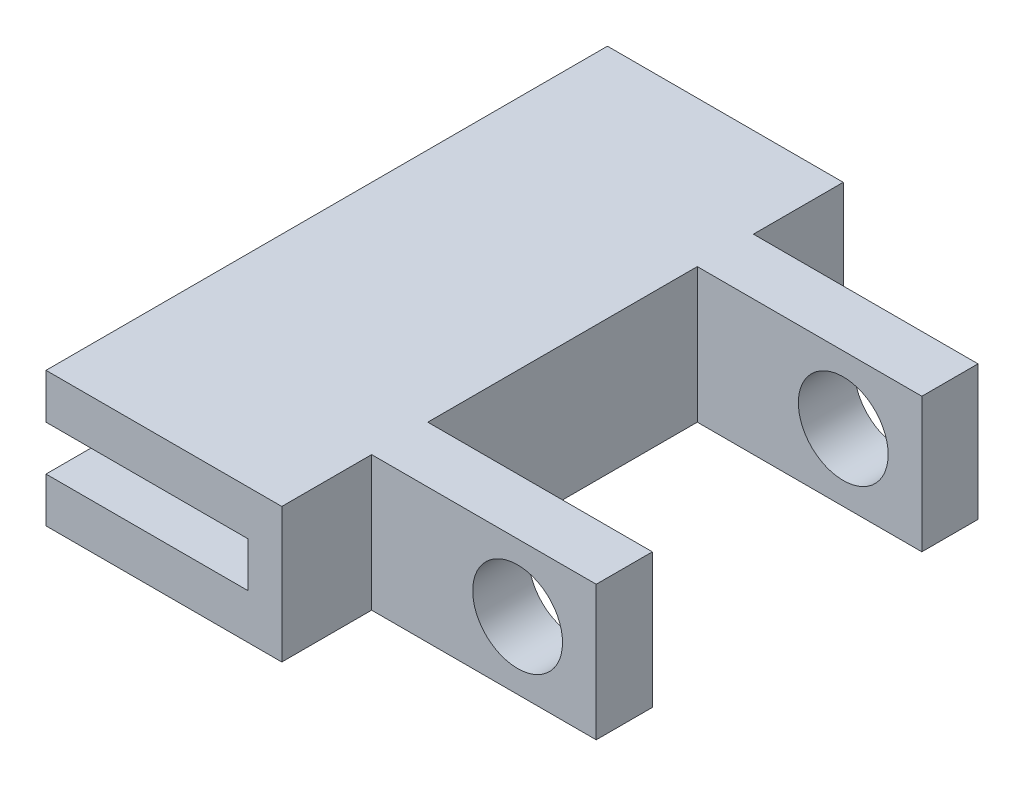
SolidWorks part; units mm, degrees
ref_plane "前视基准面" through (0, 0, 0) normal (0, 0, 1) x (1, 0, 0)
ref_plane "上视基准面" through (0, 0, 0) normal (0, 1, 0) x (1, 0, 0)
ref_plane "右视基准面" through (0, 0, 0) normal (1, 0, 0) x (0, 0, -1)
sketch "草图1" plane through (0, 0, 0) normal (0, 0, 1) x (1, 0, 0)
  line L0 (-12.5533, 0) -> (5.4467, 0)
  line L1 (5.4467, 0) -> (5.4467, 4)
  line L2 (5.4467, 4) -> (-12.5533, 4)
  line L3 (-12.5533, 8) -> (8.4467, 8)
  line L4 (8.4467, 8) -> (8.4467, -4)
  line L5 (8.4467, -4) -> (-12.5533, -4)
  line L6 (-12.5533, -4) -> (-12.5533, 0)
  line L7 (-12.5533, 4) -> (-12.5533, 8)
  dimension "D1" = 18
  dimension "D2" = 4
  dimension "D3" = 4
  dimension "D4" = 18
  dimension "D5" = 4
  dimension "D6" = 3
extrude "凸台-拉伸1" add sketch "草图1" along normal blind 25 and the other way blind 25 contours L3 L4 L5 L6 L0 L1 L2 L7
sketch "草图2" plane through (8.4467, 0, 0) normal (1, 0, 0) x (0, 0, -1)
  line L0 (0, 8) -> (0, -4) construction
  line L1 (25, 8) -> (-25, 8) construction
  line L2 (25, -4) -> (-25, -4) construction
  line L3 (-12, 8) -> (-12, -4)
  line L4 (-12, -4) -> (-17, -4)
  line L5 (-17, -4) -> (-17, 8)
  line L6 (-17, 8) -> (-12, 8)
  line L7 (25, 8) -> (-25, 8)
  line L8 (-25, 8) -> (-25, -4)
  line L9 (-25, -4) -> (25, -4)
  line L10 (25, -4) -> (25, 8)
  line L11 (25, 8) -> (-25, 8) construction
  line L12 (-25, 8) -> (-25, -4) construction
  line L13 (-25, -4) -> (25, -4) construction
  line L14 (25, -4) -> (25, 8) construction
  line L15 (17, 8) -> (12, 8)
  line L16 (17, -4) -> (17, 8)
  line L17 (12, -4) -> (17, -4)
  line L18 (12, 8) -> (12, -4)
  dimension "D2" = 5
  dimension "D3" = 12
  dimension "D1" = 0
extrude "凸台-拉伸2" add sketch "草图2" along normal blind 20
sketch "草图3" plane through (0, 0, 17) normal (0, 0, 1) x (1, 0, 0)
  line L0 (28.4467, 8) -> (28.4467, -4) construction
  circle A0 centre (21.4467, 2) radius 4
  dimension "D1" = 8
  dimension "D2" = 7
extrude "切除-拉伸1" cut sketch "草图3" against normal blind 41
